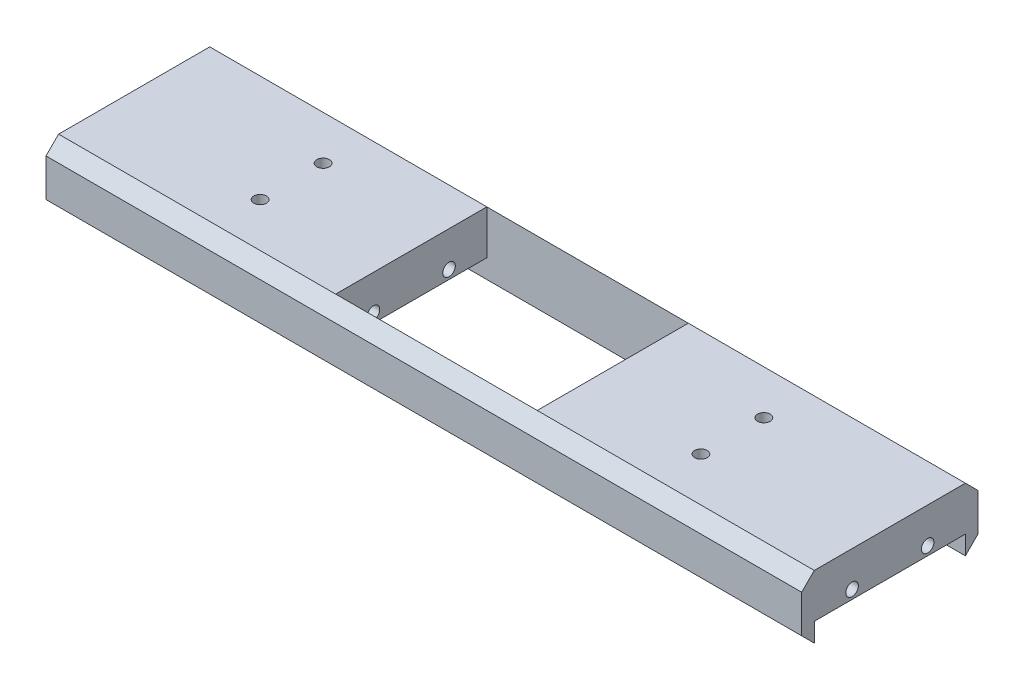
SolidWorks part; units mm, degrees
ref_plane "Front" through (0, 0, 0) normal (0, 0, 1) x (1, 0, 0)
ref_plane "Top" through (0, 0, 0) normal (0, 1, 0) x (1, 0, 0)
ref_plane "Right" through (0, 0, 0) normal (1, 0, 0) x (0, 0, -1)
sketch "草图1" plane through (0, 0, 0) normal (0, 1, 0) x (1, 0, 0)
  line L1 (30, -7) -> (-30, -7)
  line L2 (30, -7) -> (30, 7)
  line L3 (30, 7) -> (-30, 7)
  line L4 (-30, -7) -> (-30, 7)
  line L5 (30, -7) -> (-30, 7) construction
  line L6 (30, 7) -> (-30, -7) construction
  point P0 (0, 0)
  dimension "D1" = 60
  dimension "D2" = 14
extrude "凸台-拉伸1" add sketch "草图1" along normal blind 5
sketch "草图2" plane through (0, 5, 0) normal (0, 1, 0) x (1, 0, 0)
  line L1 (8, -6) -> (-8, -6)
  line L2 (8, -6) -> (8, 6)
  line L3 (8, 6) -> (-8, 6)
  line L4 (-8, -6) -> (-8, 6)
  line L5 (8, -6) -> (-8, 6) construction
  line L6 (8, 6) -> (-8, -6) construction
  point P0 (0, 0)
  dimension "D1" = 12
  dimension "D2" = 16
extrude "切除-拉伸1" cut sketch "草图2" against normal through all
sketch "草图3" plane through (-30, 0, 0) normal (-1, 0, 0) x (0, 0, 1)
  line L0 (0, 11.5474) -> (0, -8.2007) construction
  line L1 (-7, 5) -> (7, 5) construction
  circle A0 centre (-3, 2.2) radius 0.5
  circle A1 centre (3, 2.2) radius 0.5
  dimension "D1" = 1
  dimension "D2" = 6
  dimension "D3" = 2.8
extrude "切除-拉伸2" cut sketch "草图3" against normal through all
sketch "草图4" plane through (0, 0, 0) normal (0, -1, 0) x (1, 0, 0)
  line L0 (0, 22.6393) -> (0, -13.5668) construction
  line L1 (-30, -7) -> (-30, 7) construction
  line L2 (-8, -6) -> (-30, -6)
  line L3 (-8, -6) -> (-8, 6)
  line L4 (-8, 6) -> (-30, 6)
  line L5 (-30, -6) -> (-30, 6)
  line L6 (-8, -6) -> (-30, 6) construction
  line L7 (-8, 6) -> (-30, -6) construction
  line L8 (-35.2944, 0) -> (33.6013, 0) construction
  line L9 (-8, -6) -> (-8, 6) construction
  line L10 (8, 6) -> (30, -6) construction
  line L11 (8, -6) -> (30, 6) construction
  line L12 (30, -6) -> (30, 6)
  line L13 (8, 6) -> (30, 6)
  line L14 (8, -6) -> (8, 6)
  line L15 (8, -6) -> (30, -6)
  point P3 (-19, 0)
  point P19 (19, 0)
  dimension "D1" = 12
extrude "切除-拉伸3" cut sketch "草图4" against normal blind 1.5
chamfer "倒角1" distance 1 angle 45 2 edges at (0, 5, -7) (0, 5, 7)
chamfer "倒角2" distance 1 angle 45 1 edges at (0, 0, 7)
chamfer "倒角3" distance 1 angle 45 1 edges at (0, 0, -7)
sketch "草图5" plane through (0, 5, 0) normal (0, 1, 0) x (1, 0, 0)
  line L0 (0, 17.6798) -> (0, -14.4238) construction
  line L1 (-35.1642, 0) -> (30.8663, 0) construction
  circle A0 centre (-17.5, 2.5) radius 0.5
  circle A1 centre (17.5, 2.5) radius 0.5
  circle A2 centre (17.5, -2.5) radius 0.5
  circle A3 centre (-17.5, -2.5) radius 0.5
  dimension "D1" = 1
  dimension "D2" = 35
  dimension "D3" = 5
extrude "切除-拉伸4" cut sketch "草图5" against normal through all
